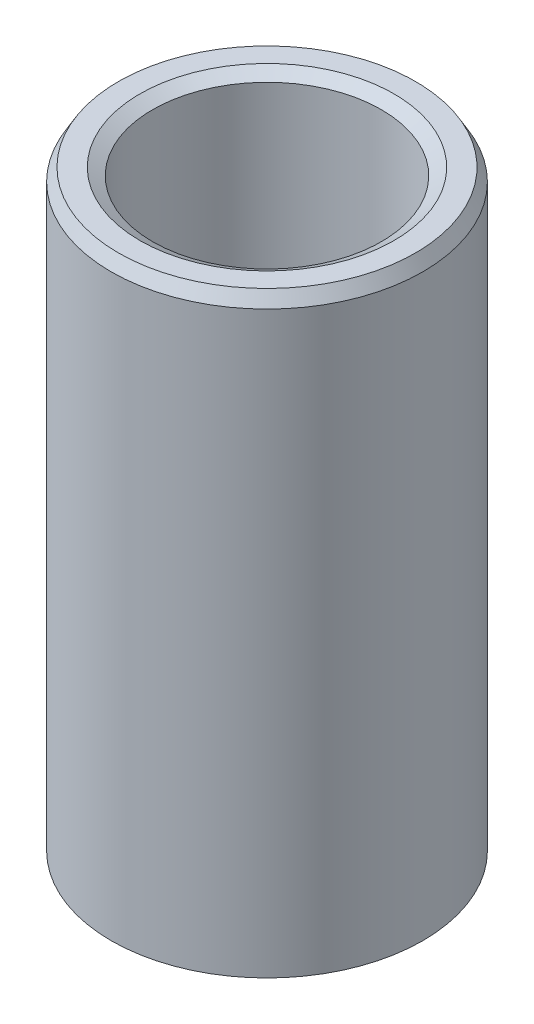
SolidWorks part; units mm, degrees
ref_plane "Front Plane" through (0, 0, 0) normal (0, 0, 1) x (1, 0, 0)
ref_plane "Top Plane" through (0, 0, 0) normal (0, 1, 0) x (1, 0, 0)
ref_plane "Right Plane" through (0, 0, 0) normal (1, 0, 0) x (0, 0, -1)
sketch "Sketch1" plane through (0, 0, 0) normal (0, 1, 0) x (1, 0, 0)
  circle A0 centre (0, 0) radius 25
  dimension "SLEEVE_OD" = 50
extrude "Boss-Extrude1" add sketch "Sketch1" along normal blind 96.1272
sketch "Sketch2" plane through (0, 0, 0) normal (0, 1, 0) x (1, 0, 0)
  circle A0 centre (0, 0) radius 18.3507
  dimension "BORE_D" = 36.7013
extrude "Cut-Extrude1" cut sketch "Sketch2" along normal through all
chamfer "Chamfer1" distance 2.0337 angle 30 4 edges at (0, 96.1272, 18.3507) (0, 0, 18.3507) (0, 0, 25) (0, 96.1272, 25) first distance on face at (0, 96.1272, 18.3507) first distance on face at (0, 0, 18.3507) first distance on face at (0, 96.1272, 25)
